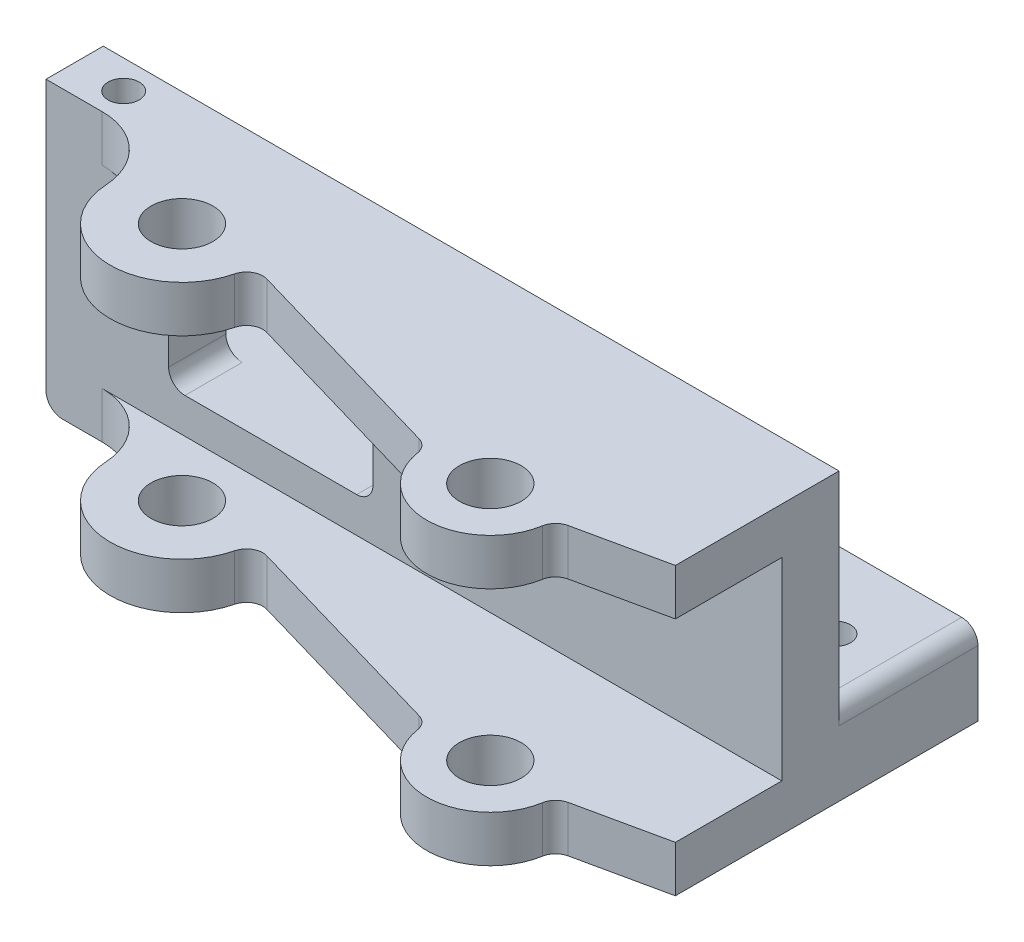
SolidWorks part; units mm, degrees
ref_plane "Front Plane" through (0, 0, 0) normal (0, 0, 1) x (1, 0, 0)
ref_plane "Top Plane" through (0, 0, 0) normal (0, 1, 0) x (1, 0, 0)
ref_plane "Right Plane" through (0, 0, 0) normal (1, 0, 0) x (0, 0, -1)
sketch "Sketch1" plane through (0, 0, 0) normal (0, 0, 1) x (1, 0, 0)
  line L1 (57.15, -22.225) -> (-57.15, -22.225)
  line L2 (57.15, -22.225) -> (57.15, 22.225)
  line L3 (57.15, 22.225) -> (-57.15, 22.225)
  line L4 (-57.15, -22.225) -> (-57.15, 22.225)
  line L5 (57.15, -22.225) -> (-57.15, 22.225) construction
  line L6 (57.15, 22.225) -> (-57.15, -22.225) construction
  point P0 (0, 0)
  dimension "D1" = 44.45
  dimension "D2" = 114.3
extrude "Boss-Extrude1" add sketch "Sketch1" along normal blind 62.23
sketch "Sketch2" plane through (0, 0, 62.23) normal (0, 0, 1) x (1, 0, 0)
  line L0 (-57.15, 22.225) -> (-57.15, -22.225) construction
  line L1 (57.15, -15.025) -> (-57.15, -15.025)
  line L2 (57.15, -15.025) -> (57.15, 15.025)
  line L3 (57.15, 15.025) -> (-57.15, 15.025)
  line L4 (-57.15, -15.025) -> (-57.15, 15.025)
  line L5 (57.15, -15.025) -> (-57.15, 15.025) construction
  line L6 (57.15, 15.025) -> (-57.15, -15.025) construction
  line L7 (57.15, 22.225) -> (-57.15, 22.225) construction
  point P0 (0, 0)
  dimension "D1" = 7.2
extrude "Cut-Extrude2" cut sketch "Sketch2" against normal blind 31.75
sketch "Sketch3" plane through (0, 0, 0) normal (0, 0, -1) x (-1, 0, 0)
  line L0 (-57.15, -22.225) -> (-57.15, 22.225) construction
  line L1 (57.15, 22.225) -> (-57.15, 22.225)
  line L2 (57.15, 22.225) -> (57.15, -9.525)
  line L3 (57.15, -9.525) -> (-57.15, -9.525)
  line L4 (-57.15, 22.225) -> (-57.15, -9.525)
  line L5 (57.15, -22.225) -> (-57.15, -22.225) construction
  dimension "D1" = 12.7
extrude "Cut-Extrude3" cut sketch "Sketch3" against normal blind 21.59
sketch "Sketch5" plane through (0, -22.225, 0) normal (0, -1, 0) x (1, 0, 0)
  line L0 (-3.81, 12.06) -> (46.99, 12.06) construction
  line L1 (57.15, 21.59) -> (-57.15, 21.59) construction
  line L2 (57.15, 62.23) -> (57.15, 0) construction
  circle A0 centre (-3.81, 12.06) radius 2.415
  circle A1 centre (46.99, 12.06) radius 2.415
  dimension "D3" = 4.83
  dimension "D4" = 10.16
  dimension "D1" = 9.53
  dimension "D2" = 50.8
extrude "Cut-Extrude4" cut sketch "Sketch5" against normal blind 25.4
sketch "Sketch7" plane through (0, -22.225, 0) normal (0, -1, 0) x (1, 0, 0)
  line L0 (57.15, 62.23) -> (57.15, 0) construction
  line L1 (-57.15, 0) -> (57.15, 0) construction
  circle A0 centre (31.75, 50.36) radius 4.8
  circle A1 centre (-27.14, 39.37) radius 4.8
  dimension "D1" = 9.6
  dimension "D2" = 25.4
  dimension "D3" = 39.37
  dimension "D4" = 9.6
  dimension "D5" = 58.89
  dimension "D6" = 10.99
extrude "Cut-Extrude6" cut sketch "Sketch7" against normal up to surface (44.45 mm away) up to face at (0, 22.225, 41.91)
sketch "Sketch9" plane through (0, 0, 30.48) normal (0, 0, 1) x (1, 0, 0)
  line L5 (57.15, 15.025) -> (-57.15, 15.025) construction
  line L6 (-38.1, 15.025) -> (-6.35, 15.025)
  line L7 (-38.1, 15.025) -> (-38.1, -15.025)
  line L8 (-38.1, -15.025) -> (-6.35, -15.025)
  line L9 (-6.35, 15.025) -> (-6.35, -15.025)
  line L10 (-57.15, -15.025) -> (57.15, -15.025) construction
  line L11 (-57.15, 15.025) -> (-57.15, -15.025) construction
  line L12 (57.15, -15.025) -> (57.15, 15.025) construction
  dimension "D1" = 63.5
  dimension "25in" = 19.05
extrude "Cut-Extrude7" cut sketch "Sketch9" against normal through all both and the other way through all
sketch "Sketch16" plane through (0, -22.225, 0) normal (0, -1, 0) x (1, 0, 0)
  line L1 (-38.1, 30.48) -> (-57.15, 30.48) construction
  line L8 (-57.15, 62.23) -> (57.15, 62.23)
  line L9 (57.15, 62.23) -> (57.15, 47.0103)
  line L10 (57.15, 62.23) -> (57.15, 0) construction
  line L11 (-15.99, 39.37) -> (21.87, 50.36)
  line L12 (41.63, 50.36) -> (57.15, 47.0103)
  line L13 (-48.4121, 30.48) -> (-57.15, 30.48)
  line L15 (-57.15, 30.48) -> (-57.15, 62.23)
  arc A2 (41.63, 50.36) -> (21.87, 50.36) centre (31.75, 50.36) ccw
  arc A3 (-15.99, 39.37) -> (-38.2702, 40.0345) centre (-27.14, 39.37) ccw
  circle A4 centre (-27.14, 39.37) radius 4.8 construction
  circle A5 centre (31.75, 50.36) radius 4.8 construction
  arc A6 (-48.4121, 30.48) -> (-38.2702, 40.0345) centre (-48.4121, 40.64) ccw
  dimension "D1" = 6.35
  dimension "D2" = 5.08
  dimension "D3" = 10.16
extrude "Cut-Extrude8" cut sketch "Sketch16" against normal through all
fillet "Fillet1" radius 2.54 6 edges at (21.87, 18.625, 50.36) (41.63, -18.625, 50.36) (41.63, 18.625, 50.36) (-15.99, 18.625, 39.37) (-15.99, -18.625, 39.37) (21.87, -18.625, 50.36)
sketch "Sketch14" plane through (-6.35, 0, 0) normal (-1, 0, 0) x (0, 0, 1)
  line L0 (0, -15.025) -> (30.48, -15.025) construction
  line L1 (21.59, -9.525) -> (0, -9.525)
  line L2 (21.59, -9.525) -> (21.59, -15.025)
  line L3 (21.59, -15.025) -> (0, -15.025)
  line L4 (0, -9.525) -> (0, -15.025)
extrude "Boss-Extrude2" add sketch "Sketch14" along normal up to next
sketch "Sketch17" plane through (0, 0, 21.59) normal (0, 0, 1) x (1, 0, 0)
  line L1 (-6.35, -15.025) -> (-38.1, -15.025)
  line L2 (-6.35, -15.025) -> (-6.35, -9.525)
  line L3 (-6.35, -9.525) -> (-38.1, -9.525)
  line L4 (-38.1, -15.025) -> (-38.1, -9.525)
extrude "Boss-Extrude3" add sketch "Sketch17" along normal up to surface (8.89 mm away) up to face at (25.4, 0, 30.48)
sketch "Sketch18" plane through (-57.15, 0, 0) normal (-1, 0, 0) x (0, 0, 1)
  line L0 (30.48, 22.225) -> (30.48, -22.225) construction
  line L1 (21.59, 22.225) -> (30.48, 22.225)
  line L2 (21.59, 22.225) -> (21.59, -22.225)
  line L3 (21.59, -22.225) -> (30.48, -22.225)
  line L4 (30.48, 22.225) -> (30.48, -22.225)
  line L5 (21.59, 22.225) -> (30.48, -22.225) construction
  line L6 (21.59, -22.225) -> (30.48, 22.225) construction
  line L7 (30.48, -22.225) -> (0, -22.225) construction
  line L8 (21.59, -9.525) -> (21.59, 22.225) construction
  line L9 (30.48, 22.225) -> (21.59, 22.225) construction
  point P0 (26.035, 0)
sketch "Sketch20" plane through (0, 0, 21.59) normal (0, 0, -1) x (-1, 0, 0)
  line L0 (38.1, 15.025) -> (38.1, -9.525) construction
  line L1 (38.1, 38.1) -> (88.9, 38.1)
  line L2 (38.1, 38.1) -> (38.1, -38.1)
  line L3 (38.1, -38.1) -> (88.9, -38.1)
  line L4 (88.9, 38.1) -> (88.9, -38.1)
  line L5 (38.1, 38.1) -> (88.9, -38.1) construction
  line L6 (38.1, -38.1) -> (88.9, 38.1) construction
  point P0 (63.5, 0)
  point P9 (88.9, 0)
  dimension "D1" = 76.2
  dimension "D2" = 50.8
sketch "Sketch21" plane through (0, 0, 30.48) normal (0, 0, 1) x (1, 0, 0)
  line L0 (-54.61, -20.32) -> (-54.61, -19.685)
  line L13 (-54.61, 19.685) -> (-54.61, -19.685)
  line L14 (-54.61, 19.685) -> (-54.61, -19.685)
  line L16 (-50.9521, -12.485) -> (-40.64, -12.485)
  line L17 (-40.64, -12.485) -> (-40.64, -12.065)
  line L34 (-54.61, -19.685) -> (-50.9521, -19.685)
  line L35 (-50.9521, -19.685) -> (-50.9521, -12.485)
  line L36 (-50.9521, -12.485) -> (54.61, -12.485)
  line L37 (54.61, -12.485) -> (54.61, 12.485)
  line L38 (54.61, 12.485) -> (-3.81, 12.485)
  line L39 (-3.81, 12.485) -> (-3.81, -12.065)
  line L40 (-3.81, -12.065) -> (-40.64, -12.065)
  line L41 (-40.64, -12.065) -> (-40.64, 12.485)
  line L42 (-40.64, 12.485) -> (-50.9521, 12.485)
  line L43 (-50.9521, 12.485) -> (-50.9521, 19.685)
  line L44 (-50.9521, 19.685) -> (-54.61, 19.685)
  line L50 (-54.61, -19.685) -> (-50.9521, -19.685)
  line L51 (-50.9521, -19.685) -> (-50.9521, -12.485)
  line L57 (-40.64, -12.065) -> (-40.64, 12.485)
  line L58 (-40.64, 12.485) -> (-50.9521, 12.485)
  line L59 (-50.9521, 12.485) -> (-50.9521, 19.685)
  line L60 (-50.9521, 19.685) -> (-54.61, 19.685)
  dimension "D1" = 2.54
fillet "Fillet6" radius 2.54 7 edges at (-6.35, -9.525, 26.035) (-6.35, 15.025, 26.035) (-38.1, 15.025, 26.035) (-38.1, -9.525, 26.035) (57.15, -9.525, 10.795) (-57.15, -9.525, 10.795) (-57.15, -22.225, 15.24)
sketch "Sketch23" plane through (0, 22.225, 0) normal (0, 1, 0) x (1, 0, 0)
  line L0 (-57.15, -30.48) -> (-57.15, -21.59) construction
  line L1 (-57.15, -30.48) -> (-48.4121, -30.48) construction
  circle A0 centre (-49.53, -26.035) radius 2.413
  dimension "D1" = 4.826
  dimension "D2" = 7.62
  dimension "D3" = 4.445
extrude "Cut-Extrude9" cut sketch "Sketch23" against normal through all
